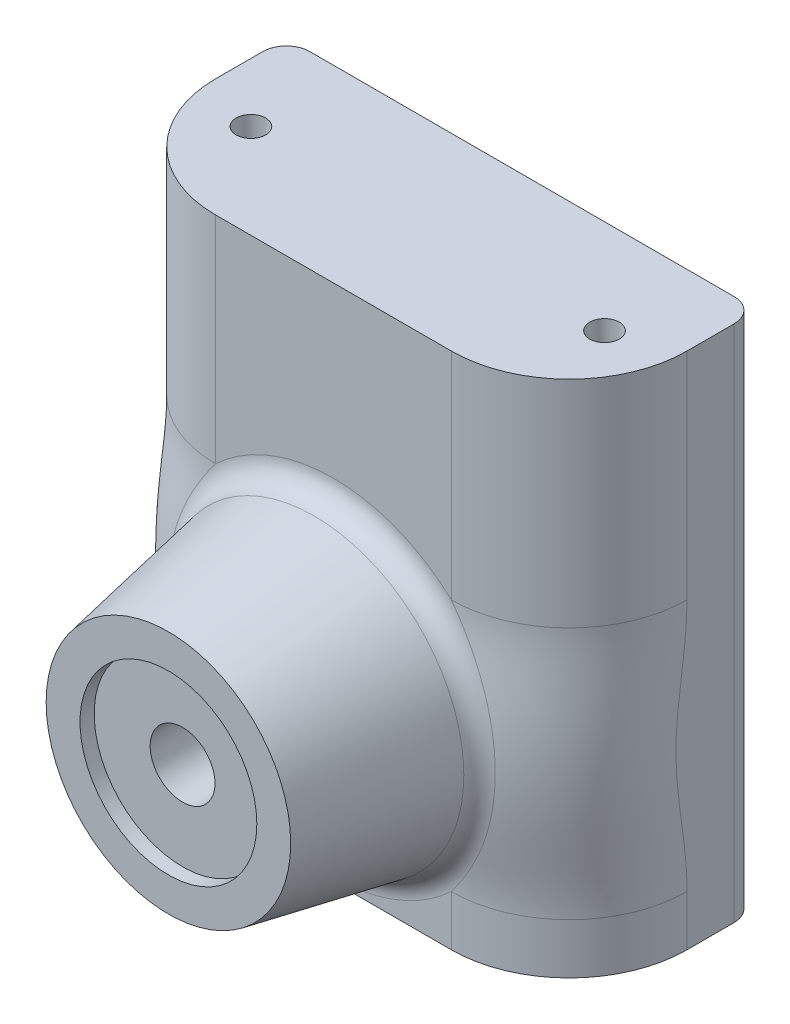
SolidWorks part; units mm, degrees
ref_plane "Спереди" through (0, 0, 0) normal (0, 0, 1) x (1, 0, 0)
ref_plane "Сверху" through (0, 0, 0) normal (0, 1, 0) x (1, 0, 0)
ref_plane "Справа" through (0, 0, 0) normal (1, 0, 0) x (0, 0, -1)
sketch "Эскиз1" plane through (0, 0, 0) normal (0, 0, 1) x (1, 0, 0)
  line L0 (0, 29) -> (0, -15) construction
  line L1 (-20, 29) -> (20, 29)
  line L2 (-20, 29) -> (-20, -15)
  line L3 (-20, -15) -> (20, -15)
  line L4 (20, 29) -> (20, -15)
  line L6 (-20, 0) -> (20, 0) construction
  dimension "D1" = 40
  dimension "D2" = 29
  dimension "D3" = 15
extrude "тело" add sketch "Эскиз1" against normal blind 16
sketch "Эскиз2" plane through (0, 0, 0) normal (0, 0, 1) x (1, 0, 0)
  circle A0 centre (0, 0) radius 10
  dimension "D1" = 20
extrude "утолщение оси" add sketch "Эскиз2" along normal blind 14
sketch "Эскиз4" plane through (0, 0, 14) normal (0, 0, 1) x (1, 0, 0)
  circle A0 centre (0, 0) radius 2.75
  dimension "D1" = 5.5
extrude "ось вращения" cut sketch "Эскиз4" against normal through all
chamfer "Фаска2" distance 3 distance2 16 1 edges at (10, 0, 0) first distance on face at (10, 0, 0)
fillet "Скругление5" radius 2 1 edges at (13, 0, 0)
sketch "Эскиз7" plane through (0, 29, 0) normal (0, 1, 0) x (1, 0, 0)
  line L0 (-20, 8) -> (20, 8) construction
  line L1 (-20, 16) -> (-20, 0) construction
  line L2 (20, 16) -> (20, 0) construction
  line L3 (0, 16) -> (0, 0) construction
  line L4 (20, 16) -> (-20, 16) construction
  circle A0 centre (-15, 8) radius 1.25
  circle A1 centre (15, 8) radius 1.25
  dimension "D1" = 2.5
  dimension "D2" = 30
extrude "отверстия для шурупов" cut sketch "Эскиз7" against normal through all
fillet "Скругление7" radius 2 2 edges at (20, 7, -16) (-20, 7, -16)
sketch "Эскиз8" plane through (0, 0, 14) normal (0, 0, 1) x (1, 0, 0)
  circle A0 centre (0, 0) radius 7.5
  dimension "D1" = 15
extrude "углубление под шайбу" cut sketch "Эскиз8" against normal blind 1.2
sketch "Эскиз9" plane through (0, 0, -16) normal (0, 0, -1) x (-1, 0, 0)
  circle A0 centre (0, 0) radius 7.5
  dimension "D1" = 15
extrude "углубление под шайбу сзади" cut sketch "Эскиз9" against normal blind 1.5
fillet "Скругление8" radius 10 2 edges at (20, 7, 0) (-20, 7, 0)
